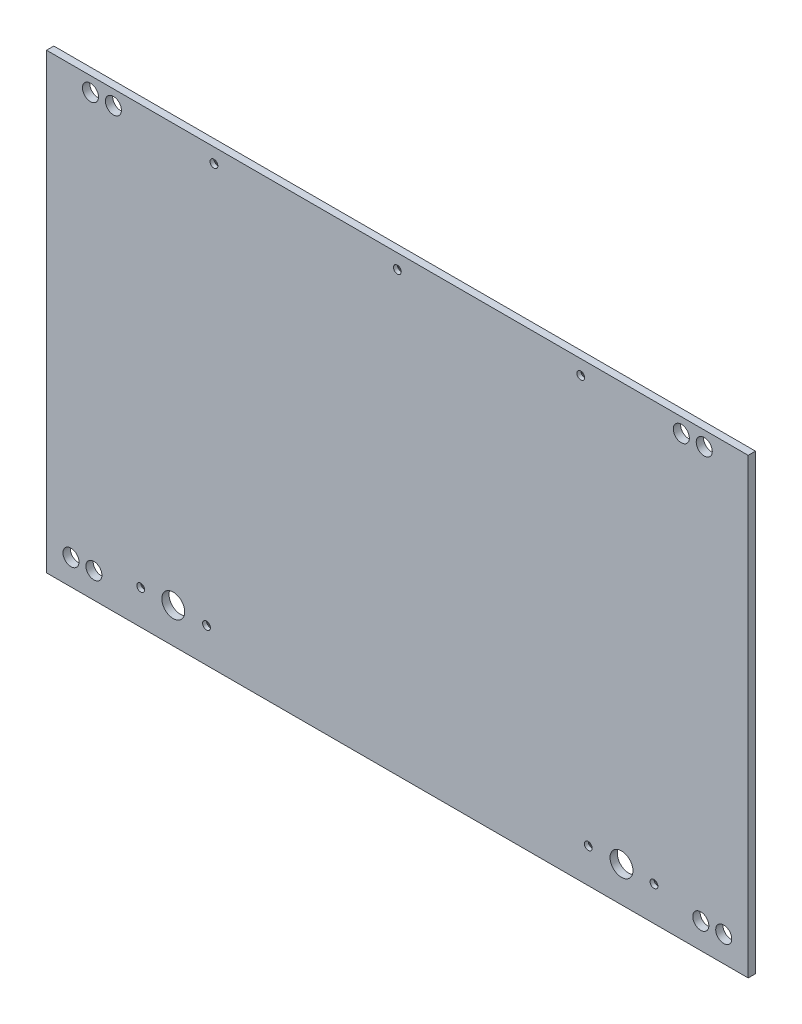
SolidWorks part; units mm, degrees
material "ABS"
ref_plane "X-Y Datum" through (0, 0, 0) normal (0, 0, 1) x (1, 0, 0)
ref_plane "X-Z Datum" through (0, 0, 0) normal (0, 1, 0) x (1, 0, 0)
ref_plane "Y-Z Datum" through (0, 0, 0) normal (1, 0, 0) x (0, 0, -1)
sketch "Sketch1" plane through (0, 0, 0) normal (0, 0, 1) x (1, 0, 0)
  line L0 (-153.025, 98.7125) -> (-153.025, -98.7125)
  line L1 (-153.025, 98.7125) -> (153.025, 98.7125)
  line L2 (-153.025, 98.7125) -> (-153.025, -98.7125)
  line L3 (-153.025, -98.7125) -> (153.025, -98.7125)
  line L4 (153.025, 98.7125) -> (153.025, -98.7125)
  line L5 (-153.025, 98.7125) -> (153.025, -98.7125) construction
  line L6 (-153.025, -98.7125) -> (153.025, 98.7125) construction
  line L7 (-153.025, -98.7125) -> (153.025, -98.7125)
  line L8 (153.025, 98.7125) -> (153.025, -98.7125)
  line L9 (-153.025, 98.7125) -> (153.025, 98.7125)
  circle A0 centre (-142.25, -87.9375) radius 10.775
  circle A1 centre (-118.25, -87.9375) radius 10.775 construction
  circle A2 centre (-130.25, -64.9375) radius 10.775
  point P0 (0, 0)
  dimension "D1" = 21.55
  dimension "D2" = 24
  dimension "D3" = 23
  dimension "D4" = 12
  dimension "D5" = 197.425
  dimension "D6" = 306.05
  dimension "D7" = 0
extrude "Boss-Extrude1" add sketch "Sketch1" along normal blind 3.175 contours A0 L3 L4 L1 L2 A2 | A2 | A0 | A0 L2 L3 | L9 L0 L7 L8 L1 L4 L3 L2 region at (1.7287, 0.9747, 0) region at (-150.6182, -96.3057, 0) region at (-142.25, -87.9375, 0) region at (-130.25, -64.9375, 0)
sketch "Sketch2" plane through (0, 0, 0) normal (0, 0, -1) x (-1, 0, 0)
  circle A1 centre (-97.75, -83.334) radius 5
  circle A2 centre (-97.75, -83.334) radius 5
  dimension "D1" = 0
extrude "Cut-Extrude1" cut sketch "Sketch2" against normal through all
mirror "Mirror1" about plane through (0, 0, 0) normal (1, 0, 0) of "Cut-Extrude1"
sketch "Sketch3" plane through (0, 0, 0) normal (0, 0, -1) x (-1, 0, 0)
  circle A0 centre (-123.85, 92.3625) radius 3.5
  circle A1 centre (-133.85, 92.3625) radius 3.5
  circle A2 centre (-132.35, -87.5375) radius 3.5
  circle A3 centre (-142.35, -87.5375) radius 3.5
  circle A4 centre (-132.35, -87.5375) radius 2.75 construction
  circle A5 centre (-132.35, -87.5375) radius 2.75 construction
  point P0 (-111.94, -83.7125)
  point P1 (-83.25, -83.7125)
  point P3 (-132.35, -87.5375)
  point P5 (-142.35, -87.5375)
  point P7 (0, 92.3625)
  point P9 (-80, 92.3625)
  point P11 (-123.85, 92.3625)
  point P13 (-133.85, 92.3625)
  dimension "D1" = 5.5
  dimension "D2" = 7
extrude "Cut-Extrude2" cut sketch "Sketch3" against normal through all
hole_wizard "CSK for M3 Flat Head Machine Screw1" positions "Sketch4" profile "Sketch5" countersink size "M3" standard "ANSI Metric" end condition through all
sketch "Sketch4" plane through (0, 0, 0) normal (0, 0, -1) x (-1, 0, 0)
  point P0 (-111.94, -83.7125)
  point P3 (-83.25, -83.7125)
  point P6 (-80, 92.3625)
  point P9 (0, 92.3625)
sketch "Sketch5" plane through (111.94, -83.7125, 0) normal (1, 0, 0) x (0, 1, 0)
  line L0 (0, 0) -> (0, 3.175)
  line L1 (0, 3.175) -> (1.7, 3.175)
  line L2 (1.7, 3.175) -> (1.7, 1.45)
  line L3 (1.7, 1.45) -> (3.15, 0)
  line L5 (3.15, 0) -> (0, 0)
  line L6 (-1.7, 1.45) -> (-3.15, 0) construction
  line L11 (0, -6.35) -> (0, 107.95) construction
  dimension "Thru Hole Dia." = 3.4
  dimension "Thru Hole Depth" = 3.175
  dimension "Near C'Sink Dia." = 6.3
  dimension "Near C'Sink Angle" = 90
mirror "Mirror2" about plane through (0, 0, 0) normal (1, 0, 0) of "Cut-Extrude2", "CSK for M3 Flat Head Machine Screw1"
